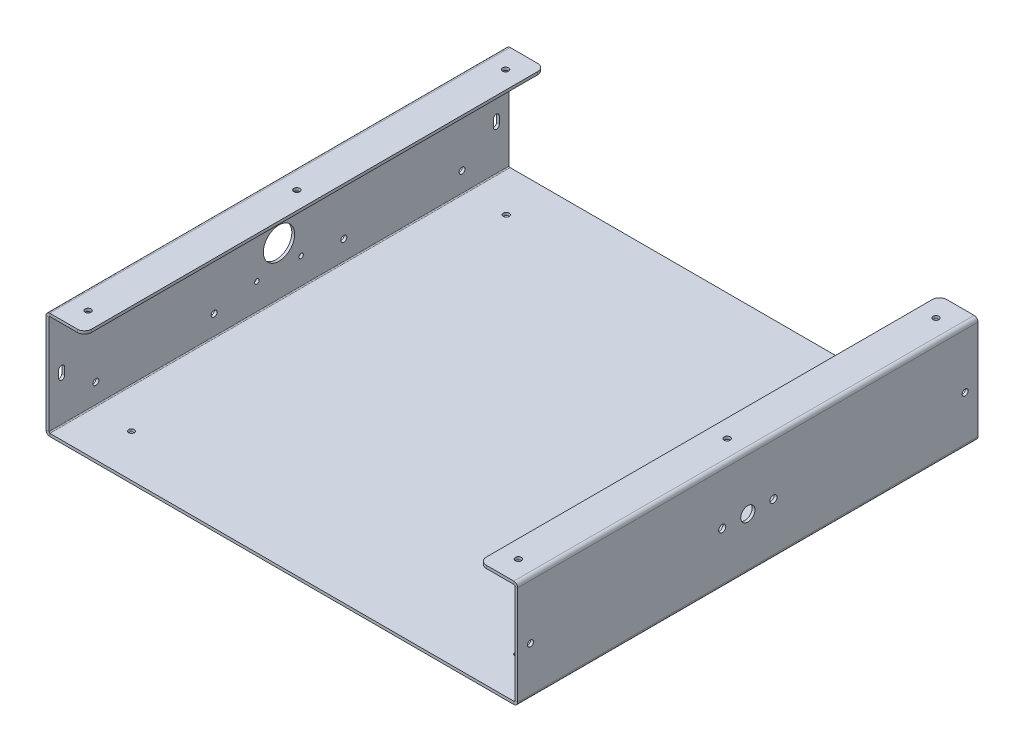
SolidWorks part; units mm, degrees
note: The reader was unsure of these and kept them because the rebuilt part matched: flange length of "Edge-Flange1", "Edge-Flange2".
ref_plane "Front Plane" through (0, 0, 0) normal (0, 0, 1) x (1, 0, 0)
ref_plane "Top Plane" through (0, 0, 0) normal (0, 1, 0) x (1, 0, 0)
ref_plane "Right Plane" through (0, 0, 0) normal (1, 0, 0) x (0, 0, -1)
sketch "Sketch1" plane through (0, 0, 0) normal (0, 0, 1) x (1, 0, 0)
  line L0 (-165.5, -37.5) -> (165.5, -37.5)
  line L1 (0, -55) -> (0, 55) construction
  line L2 (55, 0) -> (-55, 0) construction
  dimension "D1" = 331
  dimension "D2" = 165.5
  dimension "D3" = 37.5
base flange "Base-Flange1" sketch "Sketch1" end condition mid plane depth 323 reverse direction no thickness 2 reverse thickness direction yes bend radius 0.7366
edge flange "Edge-Flange1" sketch "Sketch8" flange angle 90 flange length 75 flange position material inside bend radius 0.7366 thickness 2 relief rectangular parameters "D6"=10
sketch "Sketch8" plane through (165.5, -35.5, 0) normal (-1, 0, 0) x (0, 0, 1)
  line L2 (-161.5, 0) -> (-161.5, 73)
  line L3 (-161.5, 73) -> (161.5, 73)
  line L4 (161.5, 73) -> (161.5, 0)
  line L5 (161.5, 0) -> (-161.5, 0) construction
  line L6 (161.5, 0) -> (-161.5, 0)
bend "EdgeBend1" bend radius 0.7366 bend angle 90 parameters "D5"=1
mirror "Mirror1" about plane through (0, 0, 0) normal (1, 0, 0) of "Edge-Flange1"
bend "MirrorBend1" bend radius 0.7366 bend angle 90 parameters "D5"=2
edge flange "Edge-Flange2" sketch "Sketch11" flange angle 90 flange length 27 flange position material inside bend radius 0.7366 thickness 2 relief rectangular parameters "D6"=10
sketch "Sketch11" plane through (163.5, 37.5, 0) normal (0, -1, 0) x (0, 0, 1)
  line L2 (-161.5, 0) -> (-161.5, 25)
  line L3 (-161.5, 25) -> (161.5, 25)
  line L4 (161.5, 25) -> (161.5, 0)
  line L5 (161.5, 0) -> (-161.5, 0) construction
  line L6 (161.5, 0) -> (-161.5, 0)
bend "EdgeBend2" bend radius 0.7366 bend angle 90 parameters "D5"=3
mirror "Mirror2" about plane through (0, 0, 0) normal (1, 0, 0) of "Edge-Flange2"
bend "MirrorBend2" bend radius 0.7366 bend angle 90 parameters "D5"=4
fillet "Fillet1" radius 5 4 edges at (138.5, 36.5, -161.5) (138.5, 36.5, 161.5) (-138.5, 36.5, -161.5) (-138.5, 36.5, 161.5)
sketch "Sketch12" plane through (165.5, 0, 0) normal (1, 0, 0) x (0, 0, -1)
  circle A0 centre (18, -1) radius 2.5
  circle A1 centre (-18, -1) radius 2.5
  circle A2 centre (0, -1) radius 5
  circle A3 centre (152.5, -3.5) radius 2.1
  circle A4 centre (-152.5, -3.5) radius 2.1
extrude "Cut-Extrude1" cut sketch "Sketch12" against normal up to next normal cut yes
sketch "Sketch13" plane through (-165.5, 0, 0) normal (-1, 0, 0) x (0, 0, 1)
  line L2 (154.6, -6) -> (154.6, -1)
  line L3 (150.4, -1) -> (150.4, -6)
  line L4 (-150.4, -6) -> (-150.4, -1)
  line L5 (-154.6, -1) -> (-154.6, -6)
  circle A0 centre (0, -1) radius 11
  circle A1 centre (-15.5, 14.5) radius 1.6
  circle A2 centre (15.5, 14.5) radius 1.6
  circle A3 centre (-15.5, -16.5) radius 1.6
  circle A4 centre (15.5, -16.5) radius 1.6
  arc A5 (150.4, -6) -> (154.6, -6) centre (152.5, -6) ccw
  arc A6 (154.6, -1) -> (150.4, -1) centre (152.5, -1) ccw
  arc A7 (-154.6, -6) -> (-150.4, -6) centre (-152.5, -6) ccw
  arc A8 (-150.4, -1) -> (-154.6, -1) centre (-152.5, -1) ccw
extrude "Cut-Extrude2" cut sketch "Sketch13" against normal up to next normal cut yes
sketch "Sketch14" plane through (0, 37.5, 0) normal (0, 1, 0) x (1, 0, 0)
  line L0 (-41.25, 0) -> (41.25, 0) construction
  line L1 (138.5, -156.5) -> (138.5, 156.5) construction
  line L2 (143.5, 161.5) -> (162.7634, 161.5) construction
  line L3 (162.7634, -161.5) -> (143.5, -161.5) construction
  circle A0 centre (151, 0) radius 2.1
  circle A1 centre (151, -146.5) radius 2.1
  circle A2 centre (151, 146.5) radius 2.1
  dimension "D1" = 12.5
  dimension "D2" = 15
  dimension "D3" = 15
extrude "Cut-Extrude3" cut sketch "Sketch14" against normal up to next normal cut yes
mirror "Mirror3" about plane through (0, 0, 0) normal (1, 0, 0) of "Cut-Extrude3"
sketch "Sketch15" plane through (0, -37.5, 0) normal (0, -1, 0) x (1, 0, 0)
  line L0 (-162.7634, -161.5) -> (162.7634, -161.5) construction
  line L1 (165.5, 161.5) -> (165.5, -161.5) construction
  line L2 (-162.7634, 161.5) -> (162.7634, 161.5) construction
  circle A0 centre (135.5, 131.5) radius 2
  circle A1 centre (135.5, -131.5) radius 2.1
  dimension "D1" = 4
  dimension "D2" = 30
  dimension "D3" = 30
  dimension "D4" = 30
  dimension "D5" = 30
extrude "Cut-Extrude4" cut sketch "Sketch15" against normal up to next normal cut yes
mirror "Mirror4" about plane through (0, 0, 0) normal (1, 0, 0) of "Cut-Extrude4"
sketch "Sketch16" plane through (-165.5, 0, 0) normal (-1, 0, 0) x (0, 0, 1)
  circle A9 centre (-128.5, -21.1273) radius 2.1
  circle A10 centre (-128.5, 21.1273) radius 2.1
  circle A11 centre (-45.5, -21.1273) radius 2.1
  circle A12 centre (-45.5, 21.1273) radius 2.1
  circle A13 centre (128.5, -21.1273) radius 2.1
  circle A14 centre (128.5, 21.1273) radius 2.1
  circle A15 centre (45.5, -21.1273) radius 2.1
  circle A16 centre (45.5, 21.1273) radius 2.1
extrude "Cut-Extrude5" cut sketch "Sketch16" against normal blind 10
sketch "Bend-Lines1" [suppressed] plane through (0, 0, 0) normal (0, 1, 0) x (1, 0, 0)
sketch "Bounding-Box1" [suppressed] plane through (0, 0, 0) normal (0, 1, 0) x (1, 0, 0)
sheet metal parameters "Sheet-Metal1" thickness 2 parameters "D1"=0.7366
flat pattern "Flat-Pattern1" [suppressed]
sketch "Bend-Lines2" plane through (0, 0, 0) normal (0, 1, 0) x (1, 0, 0)
sketch3d "Bounding-Box2" [suppressed]
  line L0 (331, 0, 0) -> (0, 0, 0) construction
  line L1 (331, 323, 0) -> (0, 323, 0) construction
  line L2 (331, 0, 0) -> (331, 323, 0) construction
  line L3 (0, 0, 0) -> (0, 323, 0) construction
sheet metal parameters "Sheet-Metal2" thickness 2 parameters "D1"=0.7366
flat pattern "Flat-Pattern1"
sketch "Bend-Lines2" plane through (0, -35.5, 0) normal (0, 1, 0) x (1, 0, 0)
  line L0 (164.1273, 161.5) -> (164.1273, -161.5) construction
  line L1 (164.1273, 161.5) -> (164.1273, -161.5) construction
sketch3d "Bounding-Box2" [suppressed]
  line L0 (403.2546, 0, 0) -> (0, 0, 0) construction
  line L1 (403.2546, 323, 0) -> (0, 323, 0) construction
  line L2 (403.2546, 0, 0) -> (403.2546, 323, 0) construction
  line L3 (0, 0, 0) -> (0, 323, 0) construction
bend of the flat pattern "Flatten-<EdgeBend1>1"
sheet metal parameters "Sheet-Metal3" thickness 2 parameters "D1"=0.7366
flat pattern "Flat-Pattern1"
sketch "Bend-Lines2" plane through (0, -35.5, 0) normal (0, 1, 0) x (1, 0, 0)
  line L0 (164.1273, 161.5) -> (164.1273, -161.5) construction
  line L1 (164.1273, 161.5) -> (164.1273, -161.5) construction
  line L2 (-164.1273, -161.5) -> (-164.1273, 161.5) construction
  line L3 (-164.1273, -161.5) -> (-164.1273, 161.5) construction
sketch3d "Bounding-Box2" [suppressed]
  line L0 (403.2546, 0, 0) -> (-72.2546, 0, 0) construction
  line L1 (403.2546, 323, 0) -> (-72.2546, 323, 0) construction
  line L2 (403.2546, 0, 0) -> (403.2546, 323, 0) construction
  line L3 (-72.2546, 0, 0) -> (-72.2546, 323, 0) construction
bend of the flat pattern "Flatten-<EdgeBend1>1"
bend of the flat pattern "Flatten-<MirrorBend1>1"
sheet metal parameters "Sheet-Metal4" thickness 2 parameters "D1"=0.7366
flat pattern "Flat-Pattern1"
sketch "Bend-Lines2" plane through (0, -35.5, 0) normal (0, 1, 0) x (1, 0, 0)
  line L0 (164.1273, 161.5) -> (164.1273, -161.5) construction
  line L1 (164.1273, 161.5) -> (164.1273, -161.5) construction
  line L2 (-164.1273, -161.5) -> (-164.1273, 161.5) construction
  line L3 (-164.1273, -161.5) -> (-164.1273, 161.5) construction
  line L4 (236.382, 161.5) -> (236.382, -161.5) construction
  line L5 (236.382, 161.5) -> (236.382, -161.5) construction
sketch3d "Bounding-Box2" [suppressed]
  line L0 (427.5093, 0, 0) -> (-72.2546, 0, 0) construction
  line L1 (427.5093, 323, 0) -> (-72.2546, 323, 0) construction
  line L2 (427.5093, 0, 0) -> (427.5093, 323, 0) construction
  line L3 (-72.2546, 0, 0) -> (-72.2546, 323, 0) construction
bend of the flat pattern "Flatten-<EdgeBend1>1"
bend of the flat pattern "Flatten-<MirrorBend1>1"
bend of the flat pattern "Flatten-<EdgeBend2>1"
sheet metal parameters "Sheet-Metal5" thickness 2 parameters "D1"=0.7366
flat pattern "Flat-Pattern1"
sketch "Bend-Lines2" plane through (0, -35.5, 0) normal (0, 1, 0) x (1, 0, 0)
  line L0 (164.1273, 161.5) -> (164.1273, -161.5) construction
  line L1 (164.1273, 161.5) -> (164.1273, -161.5) construction
  line L2 (-164.1273, -161.5) -> (-164.1273, 161.5) construction
  line L3 (-164.1273, -161.5) -> (-164.1273, 161.5) construction
  line L4 (236.382, 161.5) -> (236.382, -161.5) construction
  line L5 (236.382, 161.5) -> (236.382, -161.5) construction
  line L6 (-236.382, -161.5) -> (-236.382, 161.5) construction
  line L7 (-236.382, -161.5) -> (-236.382, 161.5) construction
sketch3d "Bounding-Box2" [suppressed]
  line L0 (-96.5093, 0, 0) -> (427.5093, 0, 0) construction
  line L1 (-96.5093, 323, 0) -> (427.5093, 323, 0) construction
  line L2 (-96.5093, 0, 0) -> (-96.5093, 323, 0) construction
  line L3 (427.5093, 0, 0) -> (427.5093, 323, 0) construction
bend of the flat pattern "Flatten-<EdgeBend1>1"
bend of the flat pattern "Flatten-<MirrorBend1>1"
bend of the flat pattern "Flatten-<EdgeBend2>1"
bend of the flat pattern "Flatten-<MirrorBend2>1"
sheet metal parameters "Sheet-Metal6" thickness 2 parameters "D1"=0.7366
flat pattern "Flat-Pattern1"
sketch "Bend-Lines2" plane through (0, -35.5, 0) normal (0, 1, 0) x (1, 0, 0)
  line L0 (164.1273, 161.5) -> (164.1273, -161.5) construction
  line L1 (164.1273, 161.5) -> (164.1273, -161.5) construction
  line L2 (-164.1273, -161.5) -> (-164.1273, 161.5) construction
  line L3 (-164.1273, -161.5) -> (-164.1273, 161.5) construction
  line L4 (236.382, 161.5) -> (236.382, -161.5) construction
  line L5 (236.382, 161.5) -> (236.382, -161.5) construction
  line L6 (-236.382, -161.5) -> (-236.382, 161.5) construction
  line L7 (-236.382, -161.5) -> (-236.382, 161.5) construction
sketch3d "Bounding-Box2" [suppressed]
  line L0 (-96.5093, 0, 0) -> (427.5093, 0, 0) construction
  line L1 (-96.5093, 323, 0) -> (427.5093, 323, 0) construction
  line L2 (-96.5093, 0, 0) -> (-96.5093, 323, 0) construction
  line L3 (427.5093, 0, 0) -> (427.5093, 323, 0) construction
bend of the flat pattern "Flatten-<EdgeBend1>1"
bend of the flat pattern "Flatten-<MirrorBend1>1"
bend of the flat pattern "Flatten-<EdgeBend2>1"
bend of the flat pattern "Flatten-<MirrorBend2>1"
sheet metal parameters "Sheet-Metal7" thickness 2 parameters "D1"=0.7366
flat pattern "Flat-Pattern1"
sketch "Bend-Lines2" plane through (0, -35.5, 0) normal (0, 1, 0) x (1, 0, 0)
  line L0 (164.1273, 161.5) -> (164.1273, -161.5) construction
  line L1 (164.1273, 161.5) -> (164.1273, -161.5) construction
  line L2 (-164.1273, -161.5) -> (-164.1273, 161.5) construction
  line L3 (-164.1273, -161.5) -> (-164.1273, 161.5) construction
  line L4 (236.382, 161.5) -> (236.382, -161.5) construction
  line L5 (236.382, 161.5) -> (236.382, -161.5) construction
  line L6 (-236.382, -161.5) -> (-236.382, 161.5) construction
  line L7 (-236.382, -161.5) -> (-236.382, 161.5) construction
sketch3d "Bounding-Box2" [suppressed]
  line L0 (-96.5093, 0, 0) -> (427.5093, 0, 0) construction
  line L1 (-96.5093, 323, 0) -> (427.5093, 323, 0) construction
  line L2 (-96.5093, 0, 0) -> (-96.5093, 323, 0) construction
  line L3 (427.5093, 0, 0) -> (427.5093, 323, 0) construction
bend of the flat pattern "Flatten-<EdgeBend1>1"
bend of the flat pattern "Flatten-<MirrorBend1>1"
bend of the flat pattern "Flatten-<EdgeBend2>1"
bend of the flat pattern "Flatten-<MirrorBend2>1"
sheet metal parameters "Sheet-Metal8" thickness 2 parameters "D1"=0.7366
flat pattern "Flat-Pattern1"
sketch "Bend-Lines2" plane through (0, -35.5, 0) normal (0, 1, 0) x (1, 0, 0)
  line L0 (164.1273, 161.5) -> (164.1273, -161.5) construction
  line L1 (164.1273, 161.5) -> (164.1273, -161.5) construction
  line L2 (-164.1273, -161.5) -> (-164.1273, 161.5) construction
  line L3 (-164.1273, -161.5) -> (-164.1273, 161.5) construction
  line L4 (236.382, 161.5) -> (236.382, -161.5) construction
  line L5 (236.382, 161.5) -> (236.382, -161.5) construction
  line L6 (-236.382, -161.5) -> (-236.382, 161.5) construction
  line L7 (-236.382, -161.5) -> (-236.382, 161.5) construction
sketch3d "Bounding-Box2" [suppressed]
  line L0 (-96.5093, 0, 0) -> (427.5093, 0, 0) construction
  line L1 (-96.5093, 323, 0) -> (427.5093, 323, 0) construction
  line L2 (-96.5093, 0, 0) -> (-96.5093, 323, 0) construction
  line L3 (427.5093, 0, 0) -> (427.5093, 323, 0) construction
bend of the flat pattern "Flatten-<EdgeBend1>1"
bend of the flat pattern "Flatten-<MirrorBend1>1"
bend of the flat pattern "Flatten-<EdgeBend2>1"
bend of the flat pattern "Flatten-<MirrorBend2>1"
sheet metal parameters "Sheet-Metal9" thickness 2 parameters "D1"=0.7366
flat pattern "Flat-Pattern1"
sketch "Bend-Lines2" plane through (0, -35.5, 0) normal (0, 1, 0) x (1, 0, 0)
  line L0 (164.1273, 161.5) -> (164.1273, -161.5) construction
  line L1 (164.1273, 161.5) -> (164.1273, -161.5) construction
  line L2 (-164.1273, -161.5) -> (-164.1273, 161.5) construction
  line L3 (-164.1273, -161.5) -> (-164.1273, 161.5) construction
  line L4 (236.382, 161.5) -> (236.382, -161.5) construction
  line L5 (236.382, 161.5) -> (236.382, -161.5) construction
  line L6 (-236.382, -161.5) -> (-236.382, 161.5) construction
  line L7 (-236.382, -161.5) -> (-236.382, 161.5) construction
sketch3d "Bounding-Box2" [suppressed]
  line L0 (-96.5093, 0, 0) -> (427.5093, 0, 0) construction
  line L1 (-96.5093, 323, 0) -> (427.5093, 323, 0) construction
  line L2 (-96.5093, 0, 0) -> (-96.5093, 323, 0) construction
  line L3 (427.5093, 0, 0) -> (427.5093, 323, 0) construction
bend of the flat pattern "Flatten-<EdgeBend1>1"
bend of the flat pattern "Flatten-<MirrorBend1>1"
bend of the flat pattern "Flatten-<EdgeBend2>1"
bend of the flat pattern "Flatten-<MirrorBend2>1"
sheet metal parameters "Sheet-Metal10" thickness 2 parameters "D1"=0.7366
flat pattern "Flat-Pattern1"
sketch "Bend-Lines2" plane through (0, -35.5, 0) normal (0, 1, 0) x (1, 0, 0)
  line L0 (164.1273, 161.5) -> (164.1273, -161.5) construction
  line L1 (164.1273, 161.5) -> (164.1273, -161.5) construction
  line L2 (-164.1273, -161.5) -> (-164.1273, 161.5) construction
  line L3 (-164.1273, -161.5) -> (-164.1273, 161.5) construction
  line L4 (236.382, 161.5) -> (236.382, -161.5) construction
  line L5 (236.382, 161.5) -> (236.382, -161.5) construction
  line L6 (-236.382, -161.5) -> (-236.382, 161.5) construction
  line L7 (-236.382, -161.5) -> (-236.382, 161.5) construction
sketch3d "Bounding-Box2" [suppressed]
  line L0 (-96.5093, 0, 0) -> (427.5093, 0, 0) construction
  line L1 (-96.5093, 323, 0) -> (427.5093, 323, 0) construction
  line L2 (-96.5093, 0, 0) -> (-96.5093, 323, 0) construction
  line L3 (427.5093, 0, 0) -> (427.5093, 323, 0) construction
bend of the flat pattern "Flatten-<EdgeBend1>1"
bend of the flat pattern "Flatten-<MirrorBend1>1"
bend of the flat pattern "Flatten-<EdgeBend2>1"
bend of the flat pattern "Flatten-<MirrorBend2>1"
sheet metal parameters "Sheet-Metal11" thickness 2 parameters "D1"=0.7366
flat pattern "Flat-Pattern1"
sketch "Bend-Lines2" plane through (0, -35.5, 0) normal (0, 1, 0) x (1, 0, 0)
  line L0 (164.1273, 161.5) -> (164.1273, -161.5) construction
  line L1 (164.1273, 161.5) -> (164.1273, -161.5) construction
  line L2 (-164.1273, -161.5) -> (-164.1273, 161.5) construction
  line L3 (-164.1273, -161.5) -> (-164.1273, 161.5) construction
  line L4 (236.382, 161.5) -> (236.382, -161.5) construction
  line L5 (236.382, 161.5) -> (236.382, -161.5) construction
  line L6 (-236.382, -161.5) -> (-236.382, 161.5) construction
  line L7 (-236.382, -161.5) -> (-236.382, 161.5) construction
sketch3d "Bounding-Box2" [suppressed]
  line L0 (-96.5093, 0, 0) -> (427.5093, 0, 0) construction
  line L1 (-96.5093, 323, 0) -> (427.5093, 323, 0) construction
  line L2 (-96.5093, 0, 0) -> (-96.5093, 323, 0) construction
  line L3 (427.5093, 0, 0) -> (427.5093, 323, 0) construction
bend of the flat pattern "Flatten-<EdgeBend1>1"
bend of the flat pattern "Flatten-<MirrorBend1>1"
bend of the flat pattern "Flatten-<EdgeBend2>1"
bend of the flat pattern "Flatten-<MirrorBend2>1"
sheet metal parameters "Sheet-Metal12" thickness 2 parameters "D1"=0.7366
flat pattern "Flat-Pattern1"
sketch "Bend-Lines2" plane through (0, -35.5, 0) normal (0, 1, 0) x (1, 0, 0)
  line L0 (164.1273, 161.5) -> (164.1273, -161.5) construction
  line L1 (164.1273, 161.5) -> (164.1273, -161.5) construction
  line L2 (-164.1273, -161.5) -> (-164.1273, 161.5) construction
  line L3 (-164.1273, -161.5) -> (-164.1273, 161.5) construction
  line L4 (236.382, 161.5) -> (236.382, -161.5) construction
  line L5 (236.382, 161.5) -> (236.382, -161.5) construction
  line L6 (-236.382, -161.5) -> (-236.382, 161.5) construction
  line L7 (-236.382, -161.5) -> (-236.382, 161.5) construction
sketch3d "Bounding-Box2" [suppressed]
  line L0 (-96.5093, 0, 0) -> (427.5093, 0, 0) construction
  line L1 (-96.5093, 323, 0) -> (427.5093, 323, 0) construction
  line L2 (-96.5093, 0, 0) -> (-96.5093, 323, 0) construction
  line L3 (427.5093, 0, 0) -> (427.5093, 323, 0) construction
bend of the flat pattern "Flatten-<EdgeBend1>1"
bend of the flat pattern "Flatten-<MirrorBend1>1"
bend of the flat pattern "Flatten-<EdgeBend2>1"
bend of the flat pattern "Flatten-<MirrorBend2>1"
